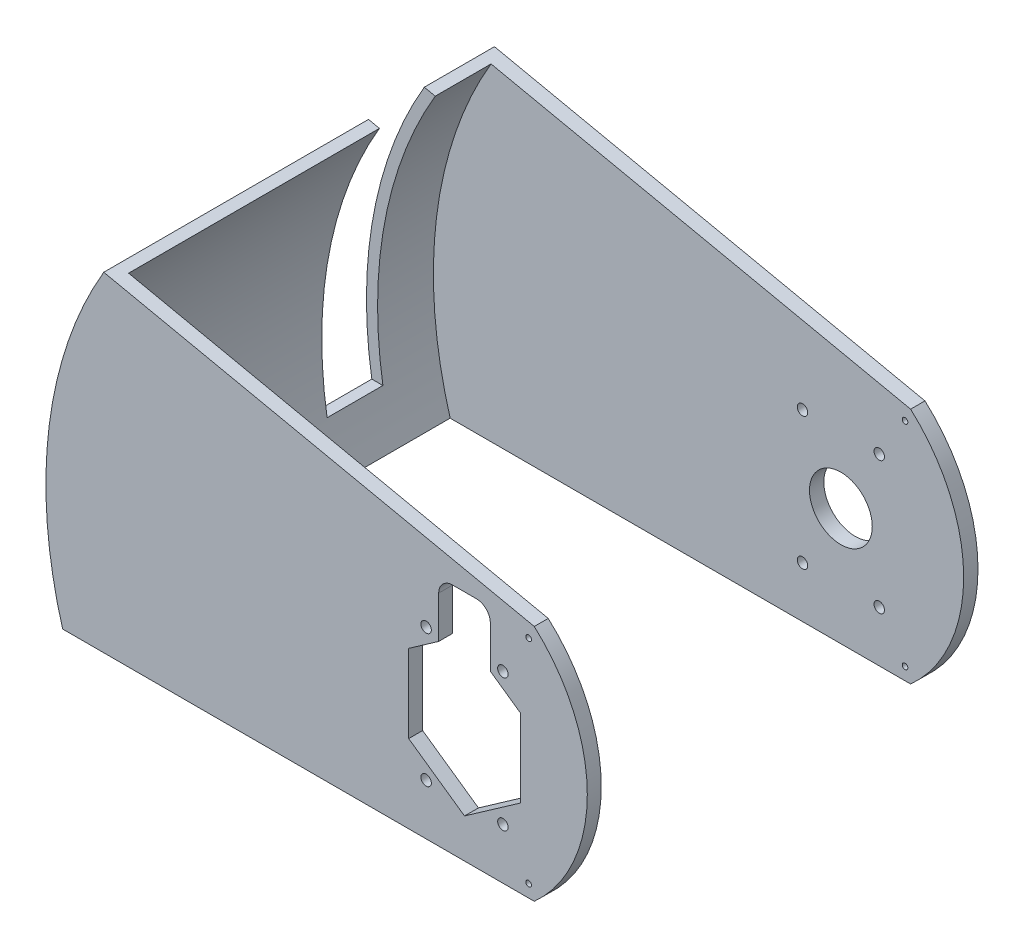
SolidWorks part; units mm, degrees
ref_plane "Front Plane" through (0, 0, 0) normal (0, 0, 1) x (1, 0, 0)
ref_plane "Top Plane" through (0, 0, 0) normal (0, 1, 0) x (1, 0, 0)
ref_plane "Right Plane" through (0, 0, 0) normal (1, 0, 0) x (0, 0, -1)
sketch "Sketch1" plane through (0, 0, 0) normal (0, 0, 1) x (1, 0, 0)
  line L0 (31.75, -53.34) -> (-182.88, -53.34)
  line L2 (-164.1695, 96.6366) -> (31.75, 54.9926)
  line L3 (31.75, 54.9926) -> (0, 0) construction
  line L4 (0, 0) -> (86.4977, 0) construction
  line L6 (-17.4625, 30.1625) -> (17.4625, 30.1625) construction
  line L7 (-17.4625, 30.1625) -> (-17.4625, -30.1625) construction
  line L8 (-17.4625, -30.1625) -> (17.4625, -30.1625) construction
  line L9 (17.4625, 30.1625) -> (17.4625, -30.1625) construction
  circle A0 centre (0, 0) radius 50.8 construction
  circle A1 centre (0, 0) radius 14.2875
  arc A4 (-164.1695, 96.6366) -> (-182.88, -53.34) centre (0, 0) ccw
  circle A8 centre (29.21, 49.1213) radius 1.27
  circle A9 centre (29.21, -47.6377) radius 1.27
  arc A10 (31.75, 54.9926) -> (31.75, -53.34) centre (-16.9805, 0.8263) cw
  circle A11 centre (-17.4625, 30.1625) radius 2.3813
  circle A12 centre (17.4625, 30.1625) radius 2.3813
  circle A13 centre (17.4625, -30.1625) radius 2.3813
  circle A14 centre (-17.4625, -30.1625) radius 2.3813
  point P19 (0, 30.1625)
  point P21 (-17.4625, 0)
  point P32 (-189.0346, 23.5832)
  point P38 (55.88, 0.8263)
  dimension "D1" = 101.6
  dimension "D2" = 28.575
  dimension "D9" = 63.5
  dimension "D10" = 57.15
  dimension "D11" = 55.88
  dimension "D13" = 190.5
  dimension "D3" = 12
  dimension "D6" = 53.34
  dimension "D4" = 2.54
  dimension "D5" = 2.54
  dimension "D7" = 55.88
  dimension "D16" = 4.7625
  dimension "D8" = 60
  dimension "D12" = 29.21
  dimension "D14" = 60.325
  dimension "D15" = 34.925
extrude "Boss-Extrude1" add sketch "Sketch1" against normal blind 177.8
sketch "Sketch2" plane through (0, -53.34, 0) normal (0, -1, 0) x (1, 0, 0)
  line L0 (-190.5, 0) -> (-190.5, -177.8) construction
  line L1 (-190.5, -6.35) -> (55.88, -6.35)
  line L2 (-190.5, -6.35) -> (-198.1119, -171.2744)
  line L3 (-198.1119, -171.2744) -> (55.88, -171.2744)
  line L6 (-182.88, 0) -> (31.75, 0) construction
  line L7 (55.88, -177.8) -> (55.88, 0) construction
  line L8 (55.88, -6.35) -> (55.88, -171.2744)
  dimension "D1" = 165.1
  dimension "D2" = 6.35
extrude "Cut-Extrude1" cut sketch "Sketch2" against normal through all
sketch "Sketch3" plane through (0, 0, -171.2744) normal (0, 0, 1) x (1, 0, 0)
  line L0 (-164.1695, 96.6366) -> (-159.2005, 95.5804)
  line L2 (-182.88, -53.34) -> (-177.8, -53.34)
  line L3 (-182.88, -53.34) -> (31.75, -53.34) construction
  arc A0 (-182.88, -53.34) -> (-164.1695, 96.6366) centre (0, 0) cw
  arc A1 (-164.1695, 96.6366) -> (-182.88, -53.34) centre (0, 0) ccw construction
  arc A2 (-177.8, -53.34) -> (-159.2005, 95.5804) centre (2.8156, -0.2764) cw
  point P14 (-189.0346, 23.5832)
  point P15 (-183.9823, 23.0538)
  dimension "D1" = 5.08
  dimension "D2" = 5.08
  dimension "D3" = 5.08
  dimension "D4" = 12
extrude "Boss-Extrude2" add sketch "Sketch3" along normal up to next (164.9244 mm away)
sketch "Sketch4" plane through (0, 0, 0) normal (1, 0, 0) x (0, 0, -1)
  line L0 (177.8, 96.6366) -> (0, 96.6366) construction
  line L1 (120.4744, 96.6366) -> (145.8744, 96.6366)
  line L2 (120.4744, 96.6366) -> (120.4744, -30.3634)
  line L3 (120.4744, -30.3634) -> (145.8744, -30.3634)
  line L4 (145.8744, 96.6366) -> (145.8744, -30.3634)
  line L5 (171.2744, 54.9926) -> (171.2744, 95.5804) construction
  dimension "D1" = 25.4
  dimension "D2" = 25.4
  dimension "D3" = 127
extrude "Cut-Extrude2" cut sketch "Sketch4" against normal through all
sketch "Sketch5" plane through (0, 0, 0) normal (0, 0, 1) x (1, 0, 0)
  line L0 (-25.4, 17.78) -> (-25.4, -17.78)
  line L1 (25.4, -17.78) -> (25.4, 17.78)
  line L2 (-25.4, -17.78) -> (0, -35.5653)
  line L4 (0, -35.5653) -> (25.4, -17.78)
  line L5 (25.4, 17.78) -> (11.7475, 27.3396)
  line L7 (-11.7475, 27.3396) -> (-25.4, 17.78)
  line L8 (-11.7475, 27.3396) -> (-11.7475, 46.3896)
  line L9 (-5.3975, 52.7396) -> (5.3975, 52.7396)
  line L10 (11.7475, 46.3896) -> (11.7475, 27.3396)
  arc A0 (-11.7475, 46.3896) -> (-5.3975, 52.7396) centre (-5.3975, 46.3896) cw
  arc A1 (5.3975, 52.7396) -> (11.7475, 46.3896) centre (5.3975, 46.3896) cw
  point P2 (0, 0)
  point P6 (0, 0)
  point P7 (0, -34.9349)
  point P9 (-25.4, 0)
  point P16 (-11.7475, 52.7396)
  point P19 (11.7475, 52.7396)
  dimension "D8" = 6.35
  dimension "D1" = 125
  dimension "D2" = 35.56
  dimension "D3" = 50.8
  dimension "D4" = 125
  dimension "D5" = 23.495
  dimension "D6" = 125
  dimension "D7" = 25.4
extrude "Cut-Extrude3" cut sketch "Sketch5" against normal up to body
